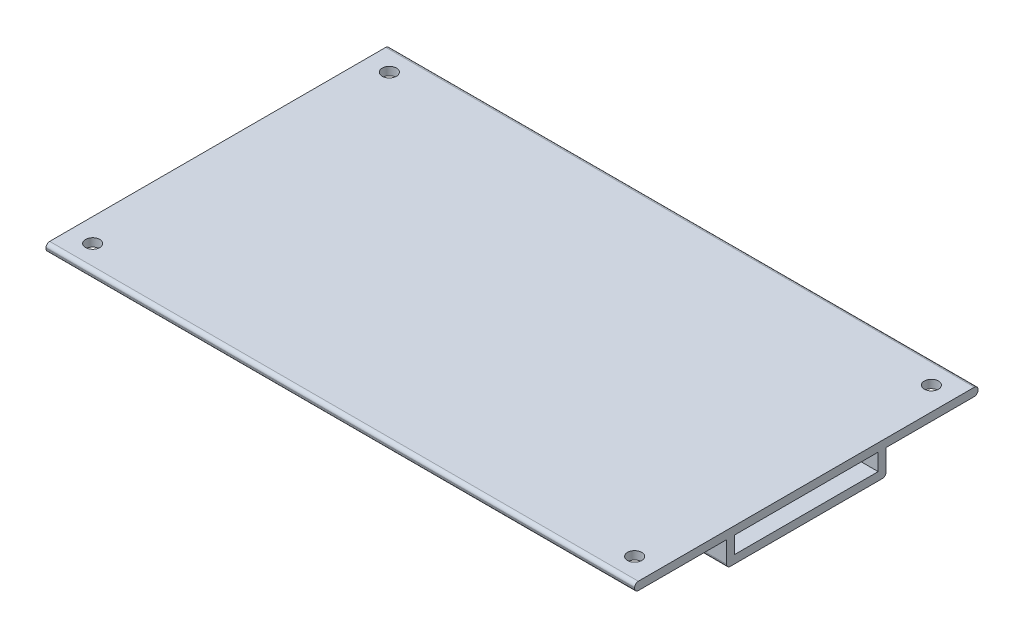
SolidWorks part; units mm, degrees
material "6061 Alloy"
ref_plane "Front Plane" through (0, 0, 0) normal (0, 0, 1) x (1, 0, 0)
ref_plane "Top Plane" through (0, 0, 0) normal (0, 1, 0) x (1, 0, 0)
ref_plane "Right Plane" through (0, 0, 0) normal (1, 0, 0) x (0, 0, -1)
sketch "Sketch1" plane through (0, 0, 0) normal (1, 0, 0) x (0, 0, -1)
  line L0 (-16.25, 0) -> (-16.25, 5.1)
  line L1 (-16.25, 5.1) -> (-35, 5.1)
  line L2 (-35, 5.1) -> (-35, 6.76)
  line L3 (-35, 6.76) -> (35, 6.76)
  line L4 (35, 6.76) -> (35, 5.1)
  line L5 (35, 5.1) -> (16.25, 5.1)
  line L6 (16.25, 5.1) -> (16.25, 0)
  line L7 (16.25, 0) -> (-16.25, 0)
  line L9 (-14.65, 5.1) -> (14.65, 5.1)
  line L10 (-14.65, 5.1) -> (-14.65, 1.66)
  line L11 (-14.65, 1.66) -> (14.65, 1.66)
  line L12 (14.65, 5.1) -> (14.65, 1.66)
  line L13 (-14.65, 5.1) -> (14.65, 1.66) construction
  line L14 (-14.65, 1.66) -> (14.65, 5.1) construction
  point P2 (0, 0)
  point P9 (0, 6.76)
  point P11 (0, 3.38)
  dimension "D1" = 70
  dimension "D2" = 1.66
  dimension "D3" = 5.1
  dimension "D4" = 32.5
  dimension "D5" = 1.66
  dimension "D6" = 1.6
extrude "Boss-Extrude1" add sketch "Sketch1" along normal blind 120
fillet "Fillet1" radius 0.75 6 edges at (60, 0, -16.25) (60, 0, 16.25) (60, 5.1, -35) (60, 6.76, -35) (60, 5.1, 35) (60, 6.76, 35)
sketch "Sketch2" plane through (0, 6.76, 0) normal (0, 1, 0) x (1, 0, 0)
  line L0 (120, 34.25) -> (120, -34.25) construction
  line L1 (0, 35) -> (120, 35) construction
  line L2 (0, 0) -> (120, 0) construction
  line L3 (0, 34.25) -> (0, -34.25) construction
  circle A0 centre (115.25, 30.25) radius 1.45
  circle A1 centre (4.75, 30.25) radius 1.45
  circle A2 centre (4.75, -30.25) radius 1.45
  circle A3 centre (115.25, -30.25) radius 1.45
  dimension "D3" = 2.9
  dimension "D6" = 2.9
  dimension "D1" = 4.75
  dimension "D2" = 4.75
  dimension "D4" = 4.75
  dimension "D5" = 4.75
extrude "Cut-Extrude1" cut sketch "Sketch2" against normal up to next
